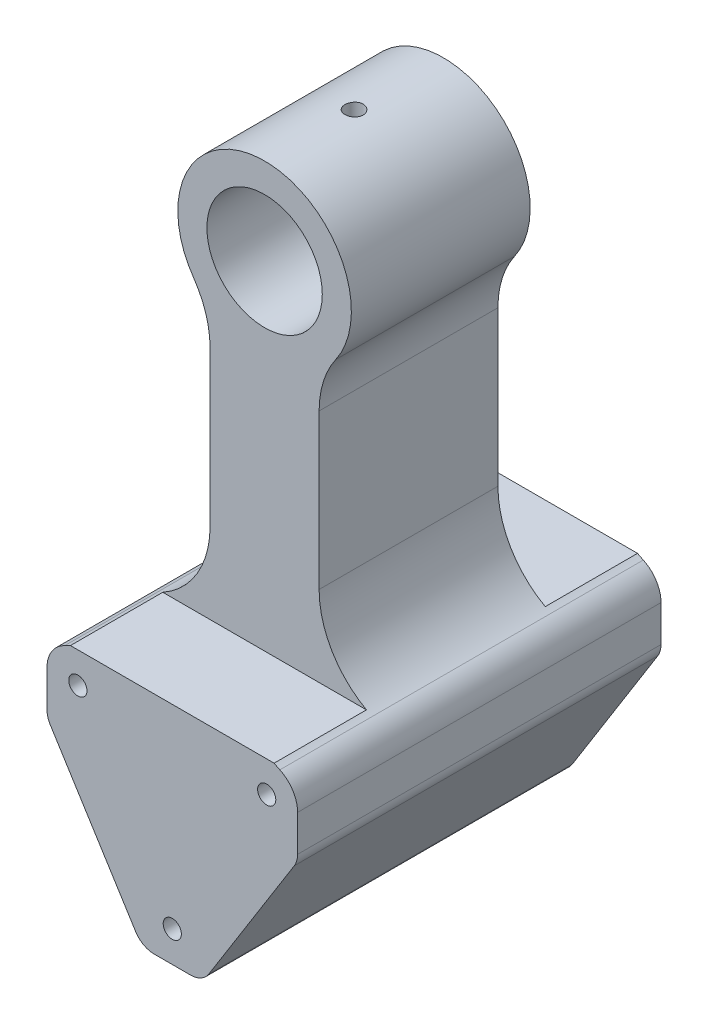
SolidWorks part; units mm, degrees
material "6061-T6 (SS)"
ref_plane "Front Plane" through (0, 0, 0) normal (0, 0, 1) x (1, 0, 0)
ref_plane "Top Plane" through (0, 0, 0) normal (0, 1, 0) x (1, 0, 0)
ref_plane "Right Plane" through (0, 0, 0) normal (1, 0, 0) x (0, 0, -1)
sketch "Sketch1" plane through (0, 0, 0) normal (0, 0, 1) x (1, 0, 0)
  line L9 (-14.0116, -46.4632) -> (14.0116, -46.4632)
  line L15 (-17.2404, -50.7132) -> (-17.2404, -55.7132)
  line L24 (-7.5, -14.1055) -> (-7.5, -35.3729)
  line L25 (7.5, -14.1055) -> (7.5, -35.3729)
  line L27 (-12.9904, -50.7132) -> (0, -58.2132) construction
  line L28 (0, -58.2132) -> (12.9904, -50.7132) construction
  line L29 (0, -73.2132) -> (0, -58.2132) construction
  line L30 (17.2404, -50.7132) -> (17.2404, -55.7132)
  line L32 (-16.7831, -57.3053) -> (-5.0427, -76.0553)
  line L33 (16.7831, -57.3053) -> (5.0427, -76.0553)
  line L34 (2.5, -77.4632) -> (-2.5, -77.4632)
  circle A0 centre (0, 0) radius 7.9375
  arc A13 (17.2404, -55.7132) -> (16.7831, -57.3053) centre (14.2404, -55.7132) cw
  arc A14 (-17.2404, -55.7132) -> (-16.7831, -57.3053) centre (-14.2404, -55.7132) ccw
  arc A18 (-2.5, -77.4632) -> (-5.0427, -76.0553) centre (-2.5, -74.4632) cw
  arc A19 (2.5, -77.4632) -> (5.0427, -76.0553) centre (2.5, -74.4632) ccw
  arc A26 (-9.7874, -6.8345) -> (9.7874, -6.8345) centre (0, 0) cw
  arc A30 (-14.7981, -46.8668) -> (-17.2404, -50.7132) centre (-12.9904, -50.7132) ccw
  circle A31 centre (0, -73.2132) radius 4.25 construction
  arc A32 (17.2404, -50.7132) -> (14.7981, -46.8668) centre (12.9904, -50.7132) ccw
  circle A33 centre (0, -73.2132) radius 1.65 construction
  circle A34 centre (12.9904, -50.7132) radius 1.65 construction
  circle A35 centre (-12.9904, -50.7132) radius 1.25 construction
  circle A36 centre (12.9904, -50.7132) radius 1.25 construction
  circle A37 centre (0, -73.2132) radius 1.25 construction
  arc A38 (-7.5, -35.3729) -> (-14.7981, -46.8668) centre (-20.2, -35.3729) cw
  arc A39 (7.5, -35.3729) -> (14.7981, -46.8668) centre (20.2, -35.3729) ccw
  arc A40 (9.7874, -6.8345) -> (7.5, -14.1055) centre (20.2, -14.1055) ccw
  arc A41 (-9.7874, -6.8345) -> (-7.5, -14.1055) centre (-20.2, -14.1055) cw
  circle A42 centre (0, -58.2132) radius 6.35 construction
  point P9 (0, 0)
  point P32 (7.5, -9.2873)
  point P35 (-7.5, -9.2873)
  point P41 (0, 0)
  point P48 (0, -77.4632)
  point P50 (0, -68.9675)
  point P51 (5.0566, -75.5458)
  point P52 (0, 0)
  point P53 (0, 0)
  dimension "D1" = 15.875
  dimension "D2" = 2.5
  dimension "D4" = 4
  dimension "D8" = 12.7
  dimension "D9" = 5
  dimension "D11" = 3
  dimension "D3" = 3
  dimension "D5" = 12.7
  dimension "D7" = 12.7
  dimension "D10" = 5
  dimension "D6" = 15
extrude "Boss-Extrude1" add sketch "Sketch1" along normal mid plane 50 contours A39 A38 A30 A31 A32 A37 A36 A35 region at (0, -59.1245, 0)
extrude "Boss-Extrude2" add sketch "Sketch1<3>" along normal mid plane 24.6 contours A0 region at (0, -20.7374, 0)
sketch "Sketch1<3>" plane through (0, 0, 0) normal (0, 0, 1) x (1, 0, 0) same geometry as "Sketch1"
sketch "Sketch3" plane through (0, 0, 0) normal (0, 1, 0) x (1, 0, 0)
  circle A0 centre (0, 0) radius 1.25
  dimension "D1" = 2.5
extrude "Cut-Extrude1" cut sketch "Sketch3" along normal through all
sketch "Sketch4" plane through (0, 0, 25) normal (0, 0, 1) x (1, 0, 0)
  circle A0 centre (-12.9904, -50.7132) radius 1.25
  circle A1 centre (12.9904, -50.7132) radius 1.25
  circle A2 centre (0, -73.2132) radius 1.25
  point P9 (0, -73.2132)
  dimension "D1" = 2.5
extrude "Cut-Extrude2" cut sketch "Sketch4" against normal blind 10
mirror "Mirror1" about plane through (0, 0, 0) normal (0, 0, 1) of "Cut-Extrude2"
